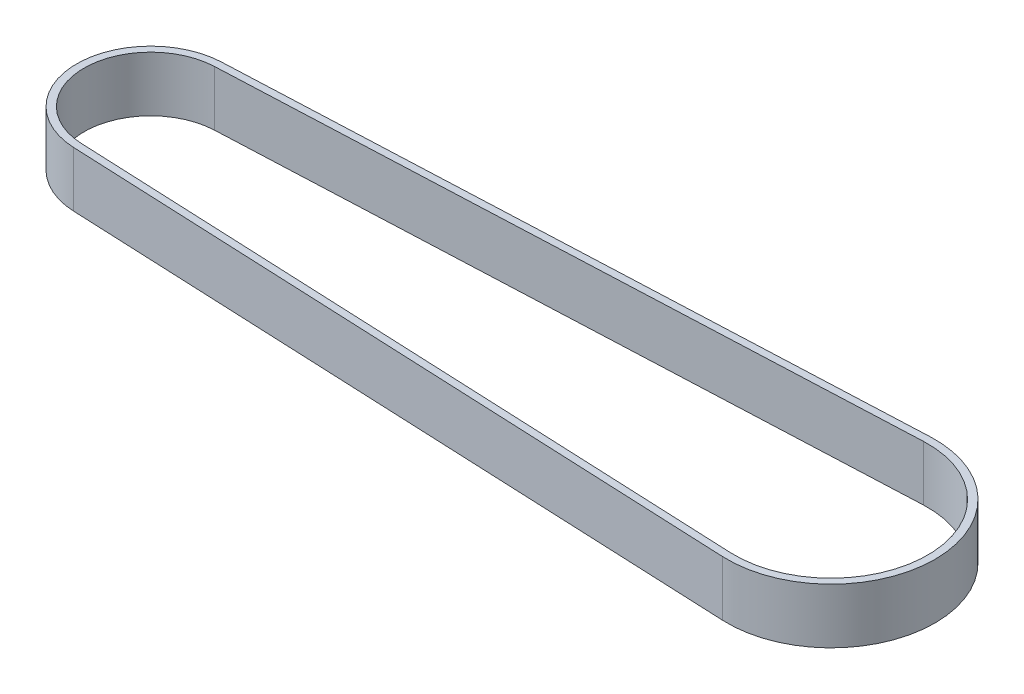
SolidWorks part; units mm, degrees
ref_plane "Front Plane" through (0, 0, 0) normal (0, 0, 1) x (1, 0, 0)
ref_plane "Top Plane" through (0, 0, 0) normal (0, 1, 0) x (1, 0, 0)
ref_plane "Right Plane" through (0, 0, 0) normal (1, 0, 0) x (0, 0, -1)
sketch "Sketch1" plane through (0, 0, 0) normal (0, 1, 0) x (1, 0, 0)
  line L0 (-74.3184, 7.243) -> (-0.4611, 10.4899)
  line L1 (-74.3184, -7.243) -> (-0.4611, -10.4899)
  line L2 (-74.3535, 8.0422) -> (-0.4963, 11.2891)
  line L3 (-74.3535, -8.0422) -> (-0.4963, -11.2891)
  arc A0 (-0.4611, -10.4899) -> (-0.4611, 10.4899) centre (0, 0) ccw
  arc A1 (-74.3184, 7.243) -> (-74.3184, -7.243) centre (-74, 0) ccw
  arc A2 (-0.4963, -11.2891) -> (-0.4963, 11.2891) centre (0, 0) ccw
  arc A3 (-74.3535, 8.0422) -> (-74.3535, -8.0422) centre (-74, 0) ccw
  dimension "D1" = 14.5
  dimension "D2" = 21
  dimension "D3" = 74
  dimension "D4" = 0.8
extrude "Boss-Extrude1" add sketch "Sketch1" along normal blind 6
ref_axis "Axis1" through (-81.25, 6, 0) along (1, 0, 0)
